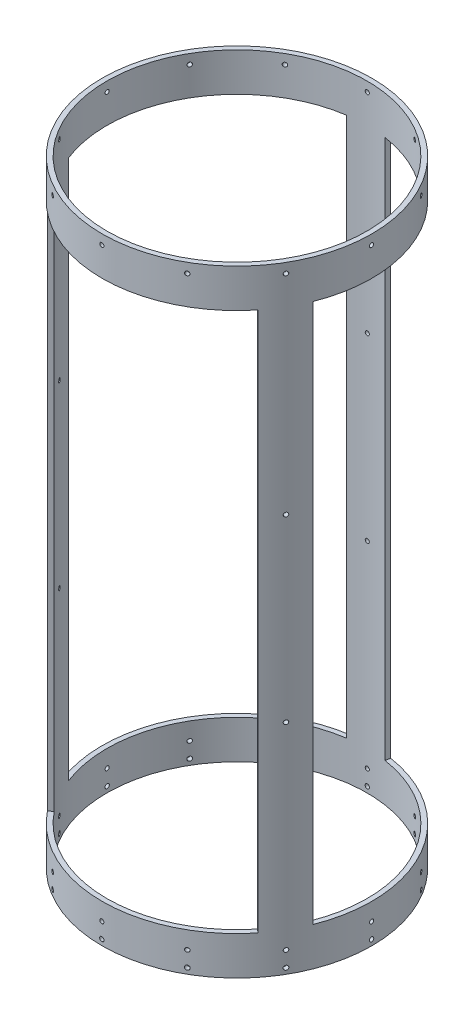
SolidWorks part; units mm, degrees
material "6061-T6 (SS)"
ref_plane "Front Plane" through (0, 0, 0) normal (0, 0, 1) x (1, 0, 0)
ref_plane "Top Plane" through (0, 0, 0) normal (0, 1, 0) x (1, 0, 0)
ref_plane "Right Plane" through (0, 0, 0) normal (1, 0, 0) x (0, 0, -1)
sketch "Sketch1" plane through (0, 0, 0) normal (0, 1, 0) x (1, 0, 0)
  circle A0 centre (0, 0) radius 88.9
  circle A1 centre (0, 0) radius 85.725
  dimension "D1" = 177.8
  dimension "D2" = 171.45
extrude "Boss-Extrude1" add sketch "Sketch1" along normal mid plane 406.4
sketch "Sketch6" plane through (0, -203.2, 0) normal (0, -1, 0) x (-1, 0, 0)
  line L0 (82.7901, -32.3885) -> (79.8333, -31.2317)
  line L1 (13.1222, 87.9262) -> (12.6536, 84.786)
  line L2 (0, 0) -> (0, 85.725) construction
  line L3 (-97.79, 0) -> (97.79, 0) construction
  line L4 (0, 0) -> (12.6536, 84.786) construction
  arc A0 (13.1222, 87.9262) -> (82.7901, -32.3885) centre (0, 0) cw
  circle A1 centre (0, 0) radius 88.9 construction
  arc A2 (12.6536, 84.786) -> (79.8333, -31.2317) centre (0, 0) cw
  circle A3 centre (0, 0) radius 85.725 construction
  arc A4 (0, 85.725) -> (12.6536, 84.786) centre (0, 0) cw construction
  dimension "D1" = 153.924
  dimension "D2" = 12.7
extrude "Cut-Extrude5" cut sketch "Sketch6" against normal blind 355.6 from offset 25.4 offset against normal yes
pattern_circular "CirPattern5" count 3 over 360 about axis through (0, -203.2, 0) along (0, 1, 0) of "Cut-Extrude5"
ref_plane "Plane1" through (0, 0, -88.9) normal (0, 0, -1) x (-1, 0, 0)
sketch "Sketch3" plane through (0, 0, 0) normal (0, 0, -1) x (-1, 0, 0)
  line L1 (-88.9, -203.2) -> (88.9, -203.2) construction
  line L3 (-12.8692, 177.8) -> (-12.8692, -177.8) construction
  circle A0 centre (-0.1692, -199.39) radius 1.4351
  circle A1 centre (-0.1692, -189.23) radius 1.3525
  dimension "D1" = 3.81
  dimension "D2" = 2.8702
  dimension "D3" = 2.7051
  dimension "D4" = 12.7
  dimension "D5" = 10.16
extrude "Cut-Extrude2" cut sketch "Sketch3" along normal up to surface (88.891 mm away) up to face at (-0.0918, 0, 72.1578)
pattern_circular "CirPattern2" count 12 over 360 about axis through (0, 203.2, 0) along (0, -1, 0) of "Cut-Extrude2" reverse direction yes
sketch "Sketch4" plane through (0, 0, -88.9) normal (0, 0, -1) x (-1, 0, 0)
  line L1 (88.9, 203.2) -> (-88.9, 203.2) construction
  circle A0 centre (-0.1692, 196.85) radius 1.3525
  dimension "D1" = 2.7051
  dimension "D2" = 6.35
extrude "Cut-Extrude3" cut sketch "Sketch4" against normal blind 15.24
pattern_circular "CirPattern3" count 12 over 360 about axis through (0, 203.2, 0) along (0, 1, 0) of "Cut-Extrude3"
ref_plane "Plane2" through (0, 0, 88.9) normal (0, 0, 1) x (1, 0, 0)
sketch "Sketch5" plane through (0, 0, 88.9) normal (0, 0, 1) x (1, 0, 0)
  line L0 (-88.9, 177.8) -> (-13.1222, 177.8) construction
  line L1 (88.9, -177.8) -> (13.3458, -177.8) construction
  circle A0 centre (0.1692, 59.2667) radius 1.3526
  circle A1 centre (0.1692, -59.2667) radius 1.3526
  dimension "D1" = 118.5333
  dimension "D2" = 118.5333
  dimension "D3" = 2.7051
  dimension "D4" = 2.7051
extrude "Cut-Extrude4" cut sketch "Sketch5" against normal up to surface (177.787 mm away) up to face at (-77.2806, 196.2438, -43.9383)
pattern_circular "CirPattern4" count 3 over 360 about axis through (0, 203.2, 0) along (0, -1, 0) of "Cut-Extrude4"
